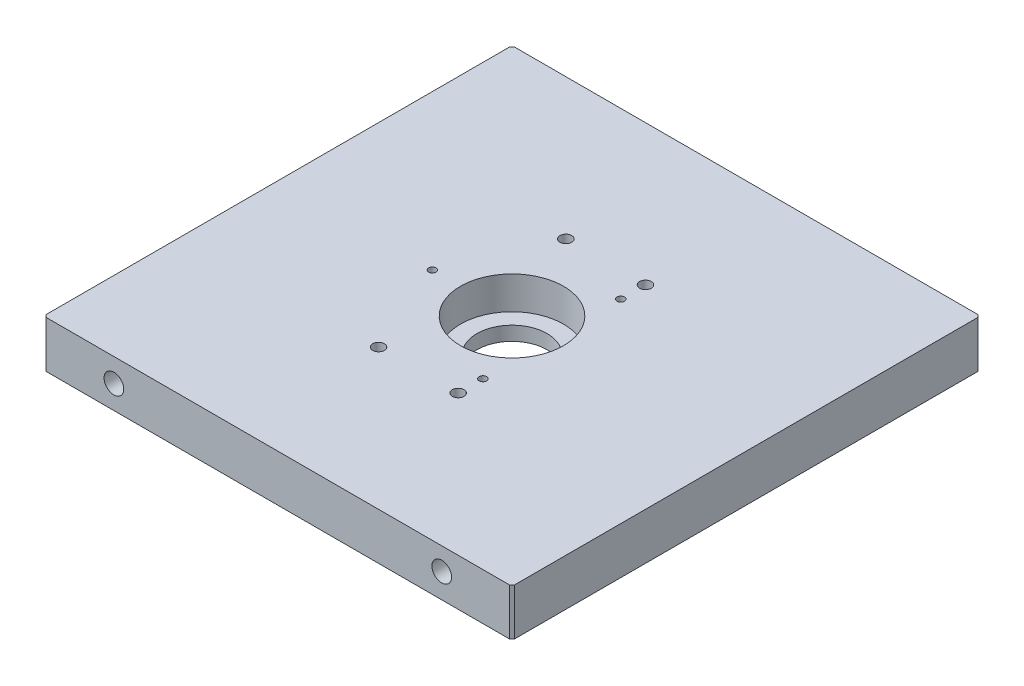
SolidWorks part; units mm, degrees
material "6061 Alloy"
ref_plane "Front Plane" through (0, 0, 0) normal (0, 0, 1) x (1, 0, 0)
ref_plane "Top Plane" through (0, 0, 0) normal (0, 1, 0) x (1, 0, 0)
ref_plane "Right Plane" through (0, 0, 0) normal (1, 0, 0) x (0, 0, -1)
sketch "Sketch1" plane through (0, 0, 0) normal (0, 1, 0) x (1, 0, 0)
  line L1 (-50, 50) -> (50, 50)
  line L2 (-50, 50) -> (-50, -50)
  line L3 (-50, -50) -> (50, -50)
  line L4 (50, 50) -> (50, -50)
  circle A0 centre (0, 0) radius 7.5
  dimension "D3" = 100
  dimension "D4" = 15
  dimension "D1" = 50
  dimension "D2" = 50
extrude "Boss-Extrude1" add sketch "Sketch1" along normal blind 5 and the other way blind 5
sketch "Sketch2" plane through (0, 5, 0) normal (0, 1, 0) x (1, 0, 0)
  circle A0 centre (0, 0) radius 11
  dimension "D1" = 22
extrude "Cut-Extrude1" cut sketch "Sketch2" against normal blind 7
hole_wizard "Tap Drill for M5x0.8 Tap1" positions "Sketch5" profile "Sketch6" hole size "M5x0.8" standard "ANSI Metric"
sketch "Sketch5" plane through (0, 0, 50) normal (0, 0, 1) x (1, 0, 0)
  line L0 (-50, -5) -> (-50, 5) construction
  line L1 (50, -5) -> (50, 5) construction
  line L2 (-50, 5) -> (50, 5) construction
  point P0 (-35, 0)
  point P2 (35, 0.2375)
  dimension "D1" = 15
  dimension "D2" = 15
  dimension "D3" = 4.7625
sketch "Sketch6" plane through (-35, 0, 50) normal (1, 0, 0) x (0, -1, 0)
  line L0 (0, 0) -> (0, 11.2618)
  line L1 (0, 11.2618) -> (2.1, 10)
  line L2 (2.1, 10) -> (2.1, 0)
  line L5 (2.1, 0) -> (0, 0)
  line L10 (0, 11.2618) -> (-2.1, 10) construction
  line L11 (0, -6.35) -> (0, 107.95) construction
  dimension "Hole Dia." = 4.2
  dimension "Hole Depth" = 10
  dimension "Drill Angle" = 118
ref_plane "Plane1" through (0, 0, 0) normal (0, 0, -1) x (-1, 0, 0)
mirror "Mirror1" about plane through (0, 0, 0) normal (0, 0, -1) of "Tap Drill for M5x0.8 Tap1"
hole_wizard "Tap Drill for M3x0.5 Tap2" positions "Sketch11" profile "Sketch12" hole size "M3x0.5" standard "ANSI Metric"
sketch "Sketch11" plane through (0, 5, 0) normal (0, 1, 0) x (1, 0, 0)
  line L0 (0, 23.6539) -> (0, -21.2998) construction
  line L3 (5.5, 0) -> (-5.5, 0) construction
  point P0 (-8.5, -20)
  point P2 (8.5, -20)
  point P4 (8.5, 20)
  point P6 (-8.5, 20)
  dimension "D1" = 8.5
  dimension "D2" = 8.5
  dimension "D3" = 20
  dimension "D4" = 20
  dimension "D5" = 8.5
  dimension "D6" = 8.5
  dimension "D7" = 20
  dimension "D8" = 20
sketch "Sketch12" plane through (-8.5, 5, 20) normal (1, 0, 0) x (0, 0, 1)
  line L0 (0, 0) -> (0, 6.7511)
  line L1 (0, 6.7511) -> (1.25, 6)
  line L2 (1.25, 6) -> (1.25, 0)
  line L5 (1.25, 0) -> (0, 0)
  line L10 (0, 6.7511) -> (-1.25, 6) construction
  line L11 (0, -6.35) -> (0, 107.95) construction
  dimension "Hole Dia." = 2.5
  dimension "Hole Depth" = 6
  dimension "Drill Angle" = 118
chamfer "Chamfer1" distance 0.5 angle 45 4 edges at (-50, 0, -50) (-50, 0, 50) (50, 0, 50) (50, 0, -50)
hole_wizard "M2x0.4 Tapped Hole1" positions "Sketch13" profile "Sketch14" tap size "M2x0.4" standard "ANSI Metric"
sketch "Sketch13" plane through (0, 5, 0) normal (0, 1, 0) x (1, 0, 0)
  line L2 (5.5, 0) -> (-5.5, 0) construction
  point P0 (-17, 0)
  point P4 (8.5, -14.7224)
  point P6 (8.5, 14.7224)
  point P9 (0, 0)
  point P11 (0, 0)
  point P14 (0, 0)
  dimension "D1" = 17
  dimension "D2" = 14.7224
  dimension "D3" = 14.7224
  dimension "D4" = 17
  dimension "D5" = 17
sketch "Sketch14" plane through (-17, 5, 0) normal (1, 0, 0) x (0, 0, 1)
  line L0 (0, 0) -> (0, 3.4807)
  line L1 (0, 3.4807) -> (0.8, 3)
  line L2 (0.8, 3) -> (0.8, 0)
  line L5 (0.8, 0) -> (0, 0)
  line L10 (0, 3.4807) -> (-0.8, 3) construction
  line L11 (0, -6.35) -> (0, 107.95) construction
  dimension "Tap Drill Dia." = 1.6
  dimension "Tap Drill Depth" = 3
  dimension "Drill Angle" = 118
cosmetic thread "Hole Thread1" parameters "D1"=3, "D2"=2
cosmetic thread "Hole Thread2" parameters "D1"=3, "D2"=2
cosmetic thread "Hole Thread3" parameters "D1"=3, "D2"=2
